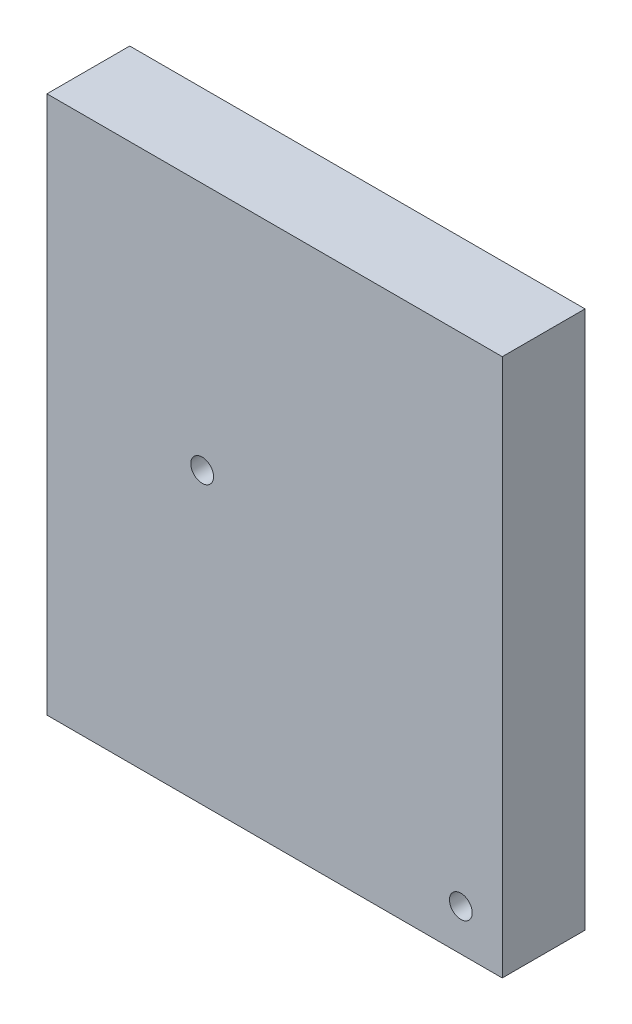
SolidWorks part; units mm, degrees
ref_plane "Front Plane" through (0, 0, 0) normal (0, 0, 1) x (1, 0, 0)
ref_plane "Top Plane" through (0, 0, 0) normal (0, 1, 0) x (1, 0, 0)
ref_plane "Right Plane" through (0, 0, 0) normal (1, 0, 0) x (0, 0, -1)
sketch "Sketch1" plane through (0, 0, 0) normal (0, 0, 1) x (1, 0, 0)
  line L1 (-27.94, -33.02) -> (27.94, -33.02)
  line L2 (-27.94, -33.02) -> (-27.94, 33.02)
  line L3 (-27.94, 33.02) -> (27.94, 33.02)
  line L4 (27.94, -33.02) -> (27.94, 33.02)
  line L5 (-27.94, -33.02) -> (27.94, 33.02) construction
  line L6 (-27.94, 33.02) -> (27.94, -33.02) construction
  circle A0 centre (-8.89, 2.54) radius 1.397
  circle A1 centre (22.86, -27.94) radius 1.397
  point P0 (0, 0)
  dimension "D3" = 2.794
  dimension "D4" = 2.794
  dimension "D1" = 55.88
  dimension "D2" = 66.04
  dimension "D5" = 5.08
  dimension "D6" = 50.8
  dimension "D7" = 19.05
  dimension "D8" = 35.56
extrude "Boss-Extrude1" add sketch "Sketch1" along normal blind 10.16
